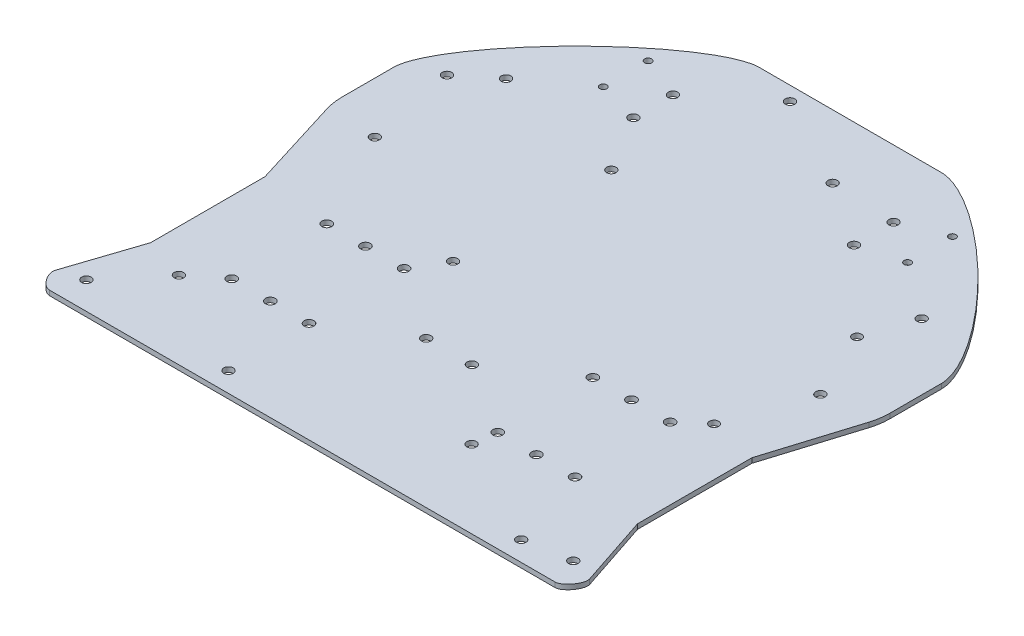
SolidWorks part; units mm, degrees
ref_plane "Front Plane" through (0, 0, 0) normal (0, 0, 1) x (1, 0, 0)
ref_plane "Top Plane" through (0, 0, 0) normal (0, 1, 0) x (1, 0, 0)
ref_plane "Right Plane" through (0, 0, 0) normal (1, 0, 0) x (0, 0, -1)
sketch "Sketch1" plane through (0, 0, 0) normal (0, 1, 0) x (1, 0, 0)
  line L0 (-90, 180) -> (-90, 0) construction
  line L1 (-180, 180) -> (0, 180)
  line L2 (-180, 180) -> (-180, 0)
  line L3 (-180, 0) -> (0, 0)
  line L4 (0, 180) -> (0, 0)
  line L5 (-180, 90) -> (0, 90) construction
  line L6 (-180, 30) -> (0, 30)
  line L7 (-130, 30) -> (-50, 30)
  line L8 (-130, 30) -> (-130, -30)
  line L9 (-130, -30) -> (-50, -30)
  line L10 (-50, 30) -> (-50, -30)
  line L11 (-130, 30) -> (-50, -30) construction
  line L12 (-130, -30) -> (-50, 30) construction
  dimension "D1" = 180
  dimension "D2" = 180
  dimension "D3" = 60
  dimension "D4" = 80
extrude "Boss-Extrude1" add sketch "Sketch1" along normal blind 1.6 contours L10 L3 L8 L9 | L2 L6 L4 L1 | L6 L10 L3 L4 | L8 L6 L2 L3 | L10 L6 L8 L3 region at (-90, 0, -105) region at (-155, 0, -15) region at (-25, 0, -15) region at (-90, 0, -15) region at (-90, 0, 15)
sketch "Sketch2" plane through (0, 1.6, 0) normal (0, 1, 0) x (1, 0, 0)
  line L0 (-180, 30) -> (0, 30)
  line L1 (-180, 180) -> (-180, 0) construction
  line L2 (0, 180) -> (0, 0) construction
  line L3 (-180, 180) -> (0, 180) construction
  line L4 (-90, 180) -> (-90, -30) construction
  line L5 (-130, -30) -> (-50, -30) construction
  dimension "D1" = 150
sketch "Sketch3" plane through (0, 1.6, 0) normal (0, 1, 0) x (1, 0, 0)
  line L0 (-180, 122) -> (0, 122)
  line L1 (-180, 180) -> (-180, 0) construction
  line L2 (0, 180) -> (0, 0) construction
  line L3 (-180, 30) -> (0, 30) construction
  dimension "D1" = 92
sketch "Sketch5" plane through (0, 1.6, 0) normal (0, 1, 0) x (1, 0, 0)
  line L0 (-114, 180) -> (-114, -30)
  line L1 (-180, 180) -> (0, 180) construction
  line L2 (-130, -30) -> (-50, -30) construction
  line L3 (-90, 180) -> (-90, -30) construction
  dimension "D1" = 24
fillet "Fillet1" radius 60 2 edges at (0, 0.8, -180) (-180, 0.8, -180) conic rho 0.2
sketch "Sketch6" plane through (0, 1.6, 0) normal (0, 1, 0) x (1, 0, 0)
  line L0 (-50, 0) -> (-130, 0)
  line L1 (-130, 0) -> (-130, -30)
  line L2 (-130, -30) -> (-50, -30)
  line L3 (-50, -30) -> (-50, 0)
  line L4 (-180, 0) -> (-170, 30.1113)
  line L5 (-170, 30.1113) -> (-170, 67.7113)
  line L6 (-170, 67.7113) -> (-180, 100)
  line L7 (-180, 120) -> (-180, 0) construction
  line L8 (-90, 180) -> (-90, -30) construction
  line L10 (-90, 180) -> (-90, 0) construction
  line L11 (0, 0) -> (-10, 30.1113)
  line L12 (-10, 30.1113) -> (-10, 67.7113)
  line L13 (-10, 67.7113) -> (0, 100)
  line M3 (0, 0) -> (0, 120)
  line M7 (-180, 120) -> (-180, 0)
  line M9 (-130, 0) -> (-130, -30)
  line M10 (-130, -30) -> (-50, -30)
  line M11 (-50, -30) -> (-50, 0)
  dimension "D1" = 37.6
  dimension "D2" = 80
  dimension "D3" = 100
extrude "Cut-Extrude1" cut sketch "Sketch6" against normal blind 10 contours L0 M11 M9 M10 | L5 L6 L4 M7 | L13 L12 L11 M3 region at (-90, 1.6, 15) region at (-175.7558, 1.6, -49.5379) region at (-4.2442, 1.6, -49.5379)
fillet "Fillet2" radius 5 2 edges at (-180, 0.8, 0) (0, 0.8, 0) conic rho 0.25
fillet "Fillet3" radius 20 2 edges at (-180, 0.8, -100) (0, 0.8, -100)
sketch "Sketch8" plane through (0, 1.6, 0) normal (0, 1, 0) x (1, 0, 0)
  circle A4 centre (-105.105, 175.3311) radius 1.55
  circle A5 centre (-74.9002, 159.1312) radius 1.55
  circle A8 centre (-115, 74.5) radius 1.55
  circle A9 centre (-115, 126.5) radius 1.55
  circle A11 centre (-146.4125, 64.417) radius 1.5875
  circle A12 centre (-133.7125, 64.417) radius 1.5875
  circle A13 centre (-121.0125, 64.417) radius 1.5875
  circle A14 centre (-146.4125, 33.175) radius 1.5875
  circle A15 centre (-133.7125, 33.175) radius 1.5875
  circle A16 centre (-121.0125, 33.175) radius 1.5875
  circle A17 centre (-58.9875, 64.417) radius 1.5875
  circle A18 centre (-46.2875, 64.417) radius 1.5875
  circle A19 centre (-33.5875, 64.417) radius 1.5875
  circle A20 centre (-33.5875, 33.175) radius 1.5875
  circle A21 centre (-46.2875, 33.175) radius 1.5875
  circle A22 centre (-58.9875, 33.175) radius 1.5875
  circle A23 centre (-59.9, 25.5) radius 1.55
  circle A24 centre (-24.6, 6.5) radius 1.55
  circle A25 centre (-120.8, 6.5) radius 1.55
  circle A26 centre (-156.1, 25.5) radius 1.55
  circle A27 centre (-27.14, 119.392) radius 1.5
  circle A28 centre (-25.87, 71.132) radius 1.5
  circle A29 centre (-169, 126.5) radius 1.55
  circle A30 centre (-126.25, 145) radius 1.55
  circle A31 centre (-53.75, 145) radius 1.55
  circle A32 centre (-170, 9) radius 1.55
  circle A33 centre (-10, 9) radius 1.55
  dimension "D3" = 3.1
  dimension "D4" = 3.1
  dimension "D5" = 3.1
  dimension "D6" = 3.1
  dimension "D7" = 3.1
  dimension "D8" = 3.175
  dimension "D9" = 3.175
  dimension "D10" = 3.175
  dimension "D11" = 3.175
  dimension "D12" = 3.175
  dimension "D13" = 3.175
  dimension "D14" = 3.1
  dimension "D15" = 3.1
  dimension "D16" = 3.1
  dimension "D17" = 3.1
  dimension "D18" = 3.175
  dimension "D19" = 3.175
  dimension "D20" = 3.175
  dimension "D21" = 3.175
  dimension "D22" = 3.175
  dimension "D23" = 3.175
  dimension "D24" = 3
  dimension "D25" = 3
  dimension "D26" = 3.1
  dimension "D27" = 3.1
  dimension "D28" = 3.1
  dimension "D29" = 3.1
extrude "Cut-Extrude2" cut sketch "Sketch8" against normal up to next (1.6 mm away)
sketch "Sketch9" plane through (0, 0, 0) normal (0, -1, 0) x (1, 0, 0)
  line L0 (-90, -180) -> (-90, 30) construction
  circle A0 centre (-163.2, -97) radius 1.55
  circle A1 centre (-158.3, -135.2) radius 1.55
  circle A2 centre (-126.25, -158) radius 1.55
  circle A3 centre (-53.75, -158) radius 1.55
  circle A4 centre (-21.7, -135.2) radius 1.55
  circle A5 centre (-16.8, -97) radius 1.55
  circle A10 centre (-140, -148.857) radius 1.143
  circle A11 centre (-140, -163.589) radius 1.143
  circle A12 centre (-40, -148.857) radius 1.143
  circle A13 centre (-40, -163.589) radius 1.143
  circle A14 centre (-97.5, -48.175) radius 1.55
  circle A15 centre (-82.5, -48.175) radius 1.55
  circle A16 centre (-121.0125, -33.175) radius 1.5875 construction
  dimension "D1" = 3.1
  dimension "D2" = 3.1
  dimension "D3" = 3.1
  dimension "D4" = 3.1
  dimension "D5" = 3.1
  dimension "D6" = 3.1
  dimension "D11" = 2.286
  dimension "D12" = 2.286
  dimension "D13" = 2.286
  dimension "D14" = 2.286
  dimension "D15" = 3.1
  dimension "D16" = 3.1
  dimension "D17" = 15
  dimension "D19" = 15
  dimension "D18" = 7.5
extrude "Cut-Extrude3" cut sketch "Sketch9" against normal up to next
